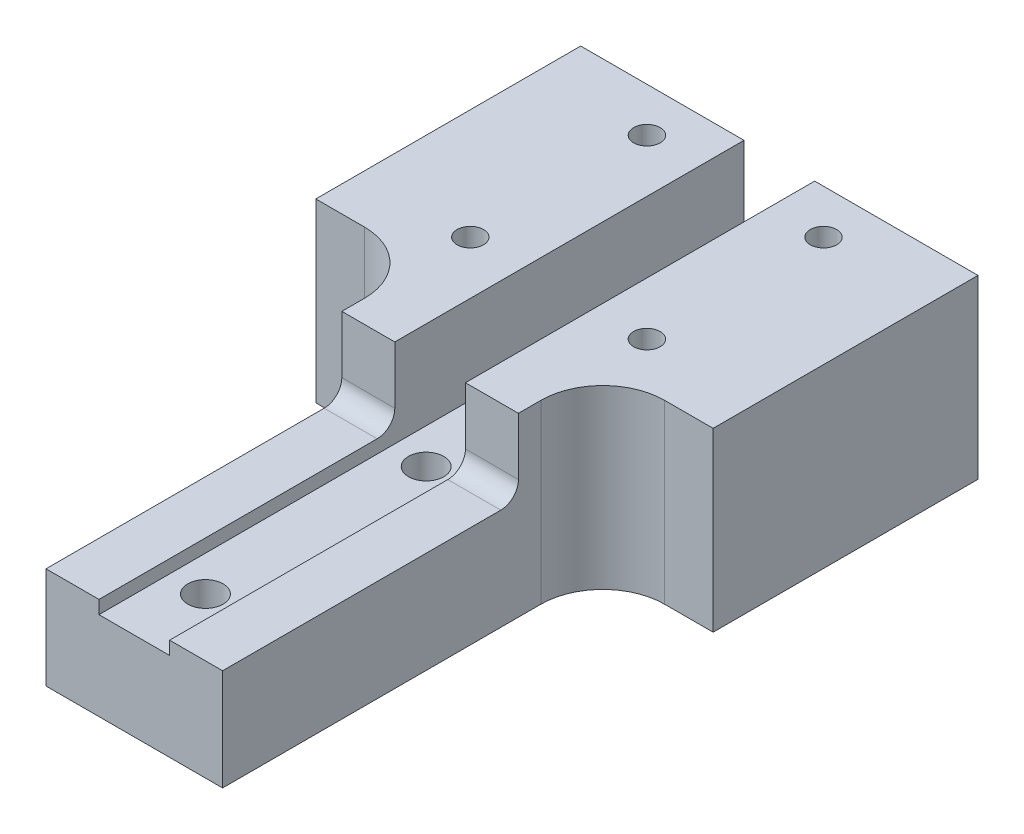
SolidWorks part; units mm, degrees
ref_plane "Front Plane" through (0, 0, 0) normal (0, 0, 1) x (1, 0, 0)
ref_plane "Top Plane" through (0, 0, 0) normal (0, 1, 0) x (1, 0, 0)
ref_plane "Right Plane" through (0, 0, 0) normal (1, 0, 0) x (0, 0, -1)
sketch "Sketch1" plane through (0, 0, 0) normal (0, 1, 0) x (1, 0, 0)
  line L0 (0, -55) -> (0, 55) construction
  line L1 (-22.5, 15) -> (22.5, 15)
  line L2 (-22.5, 15) -> (-22.5, -15)
  line L3 (-22.5, -15) -> (22.5, -15)
  line L4 (22.5, 15) -> (22.5, -15)
  line L5 (-22.5, 15) -> (22.5, -15) construction
  line L6 (-22.5, -15) -> (22.5, 15) construction
  line L7 (-10, 10) -> (10, 10)
  line L8 (-10, 10) -> (-10, -10) construction
  line L9 (-10, -10) -> (10, -10) construction
  line L10 (10, 10) -> (10, -10) construction
  line L11 (-10, 10) -> (10, -10) construction
  line L12 (-10, -10) -> (10, 10) construction
  line L13 (-10, -15) -> (10, -15)
  line L14 (-10, -15) -> (-10, -58.0584)
  line L15 (-10, -58.0584) -> (10, -58.0584)
  line L16 (10, -15) -> (10, -58.0584)
  line L17 (0, -1000) -> (0, 49000) construction
  circle A0 centre (-10, 10) radius 1.5
  circle A1 centre (10, 10) radius 1.5
  circle A2 centre (10, -10) radius 1.5
  circle A3 centre (-10, -10) radius 1.5
  circle A4 centre (0, -25) radius 2
  circle A5 centre (0, -50) radius 2
  point P0 (0, 0)
  point P6 (0, 0)
  point P26 (0, 0)
  dimension "D1" = 3
  dimension "D9" = 40
  dimension "D6" = 25
  dimension "D8" = 4
  dimension "D2" = 45
  dimension "D3" = 20
  dimension "D4" = 20
  dimension "D5" = 30
  dimension "D7" = 20
extrude "Boss-Extrude2" add sketch "Sketch1" against normal blind 20 contours L4 L1 L2 L3 A3 A2 A1 A0 | A4 | A5 | L14 L13 L16 L15 region at (0, 0, 0) region at (0, 0, 25) region at (0, 0, 50)
sketch "Sketch5" plane through (0, 0, 0) normal (0, 1, 0) x (1, 0, 0)
  line L0 (0, -55) -> (0, 55) construction
  line L1 (-4, 33.5348) -> (4, 33.5348)
  line L2 (-4, 33.5348) -> (-4, -66.4652)
  line L3 (-4, -66.4652) -> (4, -66.4652)
  line L4 (4, 33.5348) -> (4, -66.4652)
  line L5 (-4, 33.5348) -> (4, -66.4652) construction
  line L6 (-4, -66.4652) -> (4, 33.5348) construction
  point P0 (0, -16.4652)
  dimension "D1" = 8
  dimension "D2" = 100
extrude "Cut-Extrude1" cut sketch "Sketch5" against normal blind 10
fillet "Fillet1" radius 7 2 edges at (-10, -10, 15) (10, -10, 15)
ref_plane "Plane12" through (0, -8.5, 0) normal (0, 1, 0) x (1, 0, 0)
sketch "Sketch7" plane through (0, -8.5, 0) normal (0, 1, 0) x (1, 0, 0)
  line L1 (-15.6584, -24.5529) -> (14.0386, -24.5529)
  line L2 (-15.6584, -24.5529) -> (-15.6584, -59.5414)
  line L3 (-15.6584, -59.5414) -> (14.0386, -59.5414)
  line L4 (14.0386, -24.5529) -> (14.0386, -59.5414)
  line L5 (-0.8099, -59.5414) -> (-0.8099, -24.5529) construction
  line L6 (-15.6584, -42.0471) -> (14.0386, -42.0471) construction
  point P192 (-0.8099, -42.0471)
extrude "Cut-Extrude2" cut sketch "Sketch7" along normal through all
fillet "Fillet3" radius 2 2 edges at (7, -8.5, 24.5529) (-7, -8.5, 24.5529)
